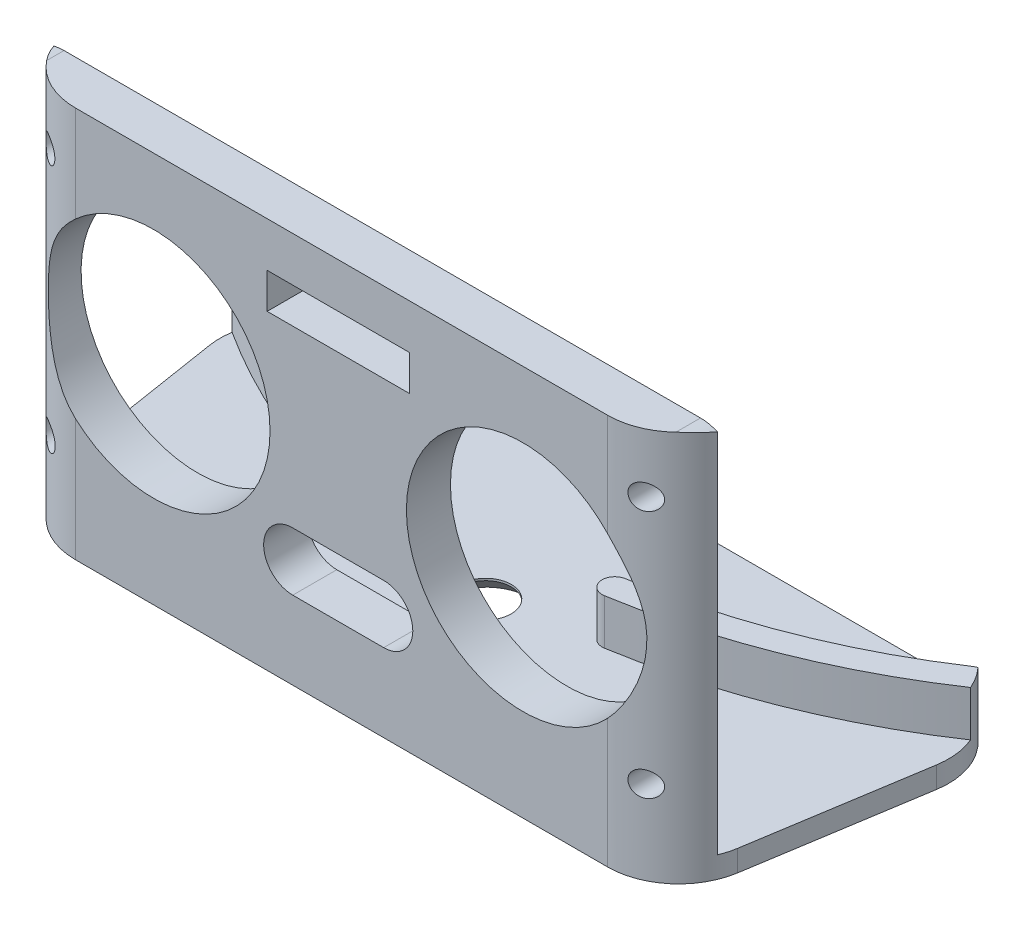
SolidWorks part; units mm, degrees
note: The reader was unsure of these and kept them because the rebuilt part matched: shared geometry of "Esquisse1<2>".
ref_plane "Plan de face" through (0, 0, 0) normal (0, 0, 1) x (1, 0, 0)
ref_plane "Plan de dessus" through (0, 0, 0) normal (0, 1, 0) x (1, 0, 0)
ref_plane "Plan de droite" through (0, 0, 0) normal (1, 0, 0) x (0, 0, -1)
sketch "Esquisse1" plane through (0, -51.3733, 0) normal (0, -1, 0) x (1, 0, 0)
  line L0 (-98.6705, -930.3284) -> (-57.3797, -930.3284)
  line L1 (-52.4413, -924.5459) -> (-54.3569, -912.4558)
  line L2 (-59.2953, -908.2383) -> (-96.755, -908.2383)
  line L3 (-101.6934, -912.4558) -> (-103.6089, -924.5459)
  line L4 (-121.3669, -930.3284) -> (-78.0251, -930.3284) construction
  line L5 (-78.0251, -930.3284) -> (-34.6833, -930.3284) construction
  line L8 (-75.0569, -908.2383) -> (-81.4569, -908.2383) construction
  arc A1 (-54.3569, -912.4558) -> (-59.2953, -908.2383) centre (-59.2953, -913.2383) ccw
  arc A2 (-96.755, -908.2383) -> (-101.6934, -912.4558) centre (-96.755, -913.2383) ccw
  arc A3 (-57.3797, -930.3284) -> (-52.4413, -924.5459) centre (-57.3797, -925.3284) ccw
  arc A4 (-98.6705, -930.3284) -> (-103.6089, -924.5459) centre (-98.6705, -925.3284) cw
  point P13 (-78.0251, -908.2383)
  point P16 (-55.0251, -908.2383)
  point P19 (-101.0251, -908.2383)
  point P22 (-51.5251, -930.3284)
  point P25 (-104.5251, -930.3284)
  dimension "D4" = 5
  dimension "D2" = 53
  dimension "D3" = 46
extrude "Boss.-Extru.1" add sketch "Esquisse1" along normal blind 1.5
sketch "Esquisse2" plane through (0, 0, -911.6383) normal (0, 0, 1) x (1, 0, 0)
  line L2 (-52.9069, -51.0733) -> (-52.9069, -31.1733)
  line L3 (-55.8569, -28.2233) -> (-100.6569, -28.2233)
  line L4 (-100.6569, -51.3733) -> (-55.8569, -51.3733)
  line L5 (-55.5569, -51.0733) -> (-55.5569, -31.1733)
  line L6 (-55.8569, -30.8733) -> (-100.6569, -30.8733)
  line L7 (-100.9569, -31.1733) -> (-100.9569, -51.0733)
  line L8 (-103.6089, -51.3733) -> (-52.9069, -51.3733)
  line L12 (-103.6069, -31.1733) -> (-103.6069, -51.0733)
  line L13 (-100.6569, -54.0233) -> (-55.8569, -54.0233) construction
  line L14 (-55.5569, -51.0733) -> (-55.5569, -31.1733) construction
  line L15 (-55.8569, -30.8733) -> (-100.6569, -30.8733) construction
  line L16 (-100.9569, -31.1733) -> (-100.9569, -51.0733) construction
  line L17 (-52.9069, -51.0733) -> (-52.9069, -51.3733)
  line L18 (-52.4413, -51.3733) -> (-54.3569, -51.3733) construction
  line L19 (-103.6069, -51.0733) -> (-103.6089, -51.3733)
  line L20 (-100.6569, -51.3733) -> (-55.8569, -51.3733) construction
  arc A1 (-52.9069, -31.1733) -> (-55.8569, -28.2233) centre (-55.8569, -31.1733) ccw
  arc A2 (-100.6569, -28.2233) -> (-103.6069, -31.1733) centre (-100.6569, -31.1733) ccw
  arc A4 (-100.9569, -51.0733) -> (-100.6569, -51.3733) centre (-100.6569, -51.0733) ccw
  arc A5 (-55.8569, -51.3733) -> (-55.5569, -51.0733) centre (-55.8569, -51.0733) ccw
  arc A6 (-55.5569, -31.1733) -> (-55.8569, -30.8733) centre (-55.8569, -31.1733) ccw
  arc A7 (-100.6569, -30.8733) -> (-100.9569, -31.1733) centre (-100.6569, -31.1733) ccw
  arc A12 (-55.8569, -54.0233) -> (-52.9069, -51.0733) centre (-55.8569, -51.0733) ccw construction
  arc A13 (-103.6069, -51.0733) -> (-100.6569, -54.0233) centre (-100.6569, -51.0733) ccw construction
  arc A14 (-100.9569, -51.0733) -> (-100.6569, -51.3733) centre (-100.6569, -51.0733) ccw construction
  arc A15 (-55.5569, -31.1733) -> (-55.8569, -30.8733) centre (-55.8569, -31.1733) ccw construction
  arc A16 (-100.6569, -30.8733) -> (-100.9569, -31.1733) centre (-100.6569, -31.1733) ccw construction
  arc A17 (-55.8569, -51.3733) -> (-55.5569, -51.0733) centre (-55.8569, -51.0733) ccw construction
  circle A18 centre (-65.2569, -41.0733) radius 8 construction
  circle A19 centre (-91.2569, -41.0733) radius 8 construction
  circle A20 centre (-99.3569, -32.3733) radius 0.83 construction
  circle A21 centre (-99.3569, -49.8733) radius 0.87 construction
  circle A22 centre (-57.1569, -49.8733) radius 0.87 construction
  circle A23 centre (-57.1569, -32.3733) radius 0.87 construction
  circle A24 centre (-65.2569, -41.0733) radius 8 construction
  circle A25 centre (-91.2569, -41.0733) radius 8 construction
  circle A26 centre (-99.3569, -32.3733) radius 0.83
  circle A27 centre (-99.3569, -49.8733) radius 0.87
  circle A28 centre (-57.1569, -49.8733) radius 0.87
  circle A29 centre (-57.1569, -32.3733) radius 0.87
  circle A30 centre (-91.2569, -41.0733) radius 8.2
  circle A32 centre (-65.2569, -41.0733) radius 8.2
  dimension "D1" = 0
  dimension "D2" = 0.2
  dimension "D3" = 0.2
extrude "Boss.-Extru.2" add sketch "Esquisse2" along normal blind 3.2 from offset 0.3
extrude "Enlèv. mat.-Extru.1" cut sketch "Esquisse1<2>" against normal through all both and the other way through all flip side to cut
sketch "Esquisse1<2>" plane through (0, -51.3733, 0) normal (0, -1, 0) x (1, 0, 0) same geometry as "Esquisse1"
sketch "Esquisse3" plane through (0, -51.3733, 0) normal (0, 1, 0) x (1, 0, 0)
  line L4 (-101.3799, 911.3383) -> (-54.6704, 911.3383)
  line L5 (-54.3569, 912.4558) -> (-52.4413, 924.5459)
  line L6 (-57.3797, 930.3284) -> (-98.6705, 930.3284)
  line L7 (-103.6089, 924.5459) -> (-101.6934, 912.4558)
  arc A0 (-53.8696, 928.8892) -> (-54.1164, 928.7571) centre (-53.288, 927.5065) ccw construction
  arc A1 (-71.5709, 921.9408) -> (-54.1164, 928.7571) centre (-78.623, 965.7553) ccw construction
  arc A2 (-71.5709, 921.9408) -> (-71.2213, 919.7687) centre (-71.3961, 920.8547) ccw construction
  arc A3 (-71.2213, 919.7687) -> (-51.7977, 927.677) centre (-78.623, 965.7553) ccw construction
  circle A4 centre (-78.4167, 918.7753) radius 1.5 construction
  arc A6 (-102.8778, 928.0301) -> (-85.1994, 921.1509) centre (-78.0202, 965.7553) ccw construction
  arc A7 (-103.6378, 925.8999) -> (-85.549, 918.9789) centre (-78.0202, 965.7553) ccw construction
  arc A8 (-85.549, 918.9789) -> (-85.1994, 921.1509) centre (-85.3742, 920.0649) ccw construction
  arc A10 (-71.5392, 921.7433) -> (-54.0059, 928.5903) centre (-78.623, 965.7553) ccw
  arc A11 (-71.5392, 921.7433) -> (-71.2531, 919.9662) centre (-71.3961, 920.8547) ccw
  arc A12 (-71.2531, 919.9662) -> (-52.0148, 927.769) centre (-78.623, 965.7553) ccw
  arc A15 (-103.6077, 926.1184) -> (-85.5172, 919.1763) centre (-78.0202, 965.7553) ccw
  arc A16 (-85.5172, 919.1763) -> (-85.2312, 920.9535) centre (-85.3742, 920.0649) ccw
  arc A17 (-102.9825, 927.8596) -> (-85.2312, 920.9535) centre (-78.0202, 965.7553) ccw
  arc A18 (-104.1835, 926.256) -> (-85.549, 918.9789) centre (-78.0202, 965.7553) ccw construction
  arc A19 (-104.0731, 926.4227) -> (-85.5172, 919.1763) centre (-78.0202, 965.7553) ccw construction
  arc A20 (-104.0653, 928.5955) -> (-85.2312, 920.9535) centre (-78.0202, 965.7553) ccw construction
  arc A21 (-104.0555, 928.833) -> (-85.1994, 921.1509) centre (-78.0202, 965.7553) ccw construction
  arc A22 (-101.6934, 912.4558) -> (-101.3799, 911.3383) centre (-96.755, 913.2383) ccw
  arc A23 (-54.6704, 911.3383) -> (-54.3569, 912.4558) centre (-59.2953, 913.2383) ccw
  arc A24 (-52.4413, 924.5459) -> (-57.3797, 930.3284) centre (-57.3797, 925.3284) ccw
  arc A25 (-98.6705, 930.3284) -> (-103.6089, 924.5459) centre (-98.6705, 925.3284) ccw
  arc A28 (-52.6904, 927.0636) -> (-53.8696, 928.8892) centre (-57.3797, 925.3284) ccw
  arc A29 (-102.8778, 928.0301) -> (-103.6378, 925.8999) centre (-98.6705, 925.3284) ccw
  arc A30 (-104.0653, 928.5955) -> (-104.0731, 926.4227) centre (-103.3552, 927.5065) ccw construction
  arc A31 (-104.0555, 928.833) -> (-104.1835, 926.256) centre (-103.3552, 927.5065) ccw construction
  arc A32 (-51.7977, 927.677) -> (-54.1164, 928.7571) centre (-53.288, 927.5065) ccw construction
  arc A33 (-53.7182, 928.7333) -> (-54.0059, 928.5903) centre (-53.288, 927.5065) ccw
  arc A34 (-52.0148, 927.769) -> (-54.0059, 928.5903) centre (-53.288, 927.5065) ccw construction
  circle A35 centre (-78.4167, 918.7753) radius 1.5
  dimension "D3" = 3
  dimension "D1" = 0.2
  dimension "D2" = 0
extrude "Boss.-Extru.3" add sketch "Esquisse3" along normal blind 3.2
sketch "Esquisse6" plane through (0, -52.8733, 0) normal (0, -1, 0) x (1, 0, 0)
  circle A11 centre (-78.4167, -918.7753) radius 1.5
  circle A12 centre (-78.4167, -918.7753) radius 1.5
  point P2 (-78.4167, -918.7753)
  dimension "D1" = 0
hole_wizard "Fraisage pour vis à tête fraisée bombée M31" positions "Esquisse6" profile "Esquisse7" countersink size "M3" standard "JIS" end condition through all
sketch "Esquisse7" plane through (-78.4167, -52.8733, -918.7753) normal (1, 0, 0) x (0, 0, -1)
  line L0 (0, 0) -> (0, 24.65)
  line L1 (0, 24.65) -> (1.8, 24.65)
  line L2 (1.8, 24.65) -> (1.8, 1.35)
  line L3 (1.8, 1.35) -> (3.15, 0)
  line L5 (3.15, 0) -> (0, 0)
  line L6 (-1.8, 1.35) -> (-3.15, 0) construction
  line L11 (0, -6.35) -> (0, 107.95) construction
  dimension "Diamètre du perçage jusqu'au prochain" = 3.6
  dimension "Profondeur du perçage jusqu'au prochain" = 24.65
  dimension "Diamètre du fraisage entrant" = 6.3
  dimension "Angle du fraisage entrant" = 90
sketch "Esquisse8" plane through (0, 0, -911.3383) normal (0, 0, -1) x (-1, 0, 0)
  line L0 (55.8569, -28.2233) -> (100.6569, -28.2233) construction
  line L1 (83.2569, -33.8733) -> (73.2569, -33.8733)
  line L2 (83.2569, -33.8733) -> (83.2569, -31.3733)
  line L3 (83.2569, -31.3733) -> (73.2569, -31.3733)
  line L4 (73.2569, -33.8733) -> (73.2569, -31.3733)
  dimension "D1" = 3.15
  dimension "D2" = 2.5
extrude "Enlèv. mat.-Extru.2" cut sketch "Esquisse8" against normal through all both and the other way through all
sketch "Esquisse9" plane through (0, 0, -908.2383) normal (0, 0, 1) x (1, 0, 0)
  line L0 (-54.6704, -51.3733) -> (-54.6704, -28.4725) construction
  line L1 (-101.3799, -51.3733) -> (-54.6704, -51.3733)
  line L2 (-101.3799, -51.3733) -> (-101.3799, -51.0633)
  line L3 (-101.3799, -51.0633) -> (-54.6704, -51.0633)
  line L4 (-54.6704, -51.3733) -> (-54.6704, -51.0633)
  dimension "D1" = 0.31
extrude "Enlèv. mat.-Extru.3" cut sketch "Esquisse9" against normal blind 10
move or copy body "Corps-Déplacer/Copier1" bodies to move or copy 109 copy no translate (0, 2.89, 0) parameters "D1"=0, "D2"=2.89, "D3"=0
sketch "Esquisse10" plane through (0, -48.1733, 0) normal (0, -1, 0) x (1, 0, 0)
  line L2 (-59.2953, -908.2383) -> (-96.755, -908.2383)
  line L3 (-101.3799, -911.3383) -> (-54.6704, -911.3383)
  line L4 (-59.2953, -908.2383) -> (-96.755, -908.2383)
  line L6 (-101.3799, -911.3383) -> (-54.6704, -911.3383)
  arc A2 (-96.755, -908.2383) -> (-101.3799, -911.3383) centre (-96.755, -913.2383) ccw
  arc A3 (-54.6704, -911.3383) -> (-59.2953, -908.2383) centre (-59.2953, -913.2383) ccw
  arc A5 (-54.6704, -911.3383) -> (-59.2953, -908.2383) centre (-59.2953, -913.2383) ccw
  arc A6 (-96.755, -908.2383) -> (-101.3799, -911.3383) centre (-96.755, -913.2383) ccw
  dimension "D1" = 0
extrude "Boss.-Extru.4" add sketch "Esquisse10" along normal blind 3.39
sketch "Esquisse11" plane through (0, 0, -908.2383) normal (0, 0, 1) x (1, 0, 0)
  line L0 (-81.4569, -45.3333) -> (-75.0569, -45.3333) construction
  line L5 (-81.4569, -43.2833) -> (-75.0569, -43.2833)
  line L6 (-81.4569, -47.3833) -> (-75.0569, -47.3833)
  line L8 (-59.2953, -52.8733) -> (-96.755, -52.8733) construction
  arc A0 (-81.4569, -43.2833) -> (-81.4569, -47.3833) centre (-81.4569, -45.3333) ccw
  arc A1 (-75.0569, -47.3833) -> (-75.0569, -43.2833) centre (-75.0569, -45.3333) ccw
  point P2 (-78.2569, -45.3333)
  dimension "D1" = 4.1
  dimension "D2" = 5.49
extrude "Enlèv. mat.-Extru.4" cut sketch "Esquisse11" against normal blind 10
